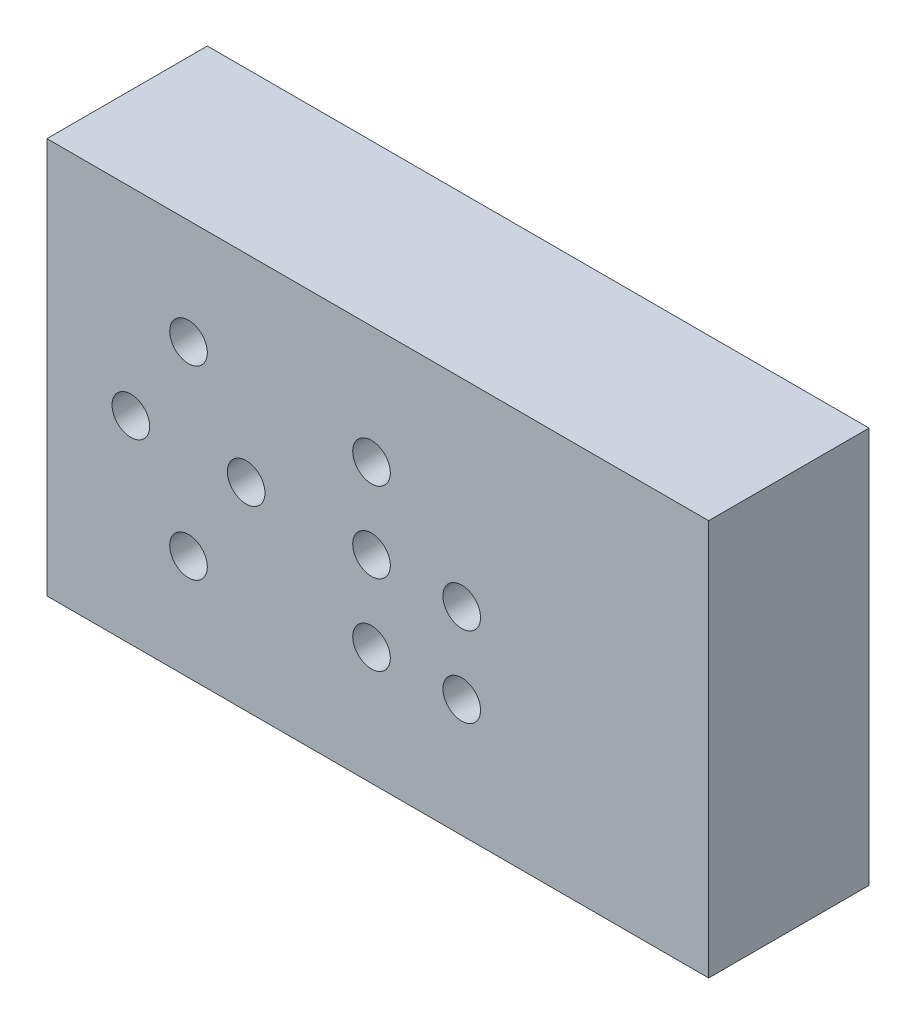
SolidWorks part; units mm, degrees
ref_plane "Front Plane" through (0, 0, 0) normal (0, 0, 1) x (1, 0, 0)
ref_plane "Top Plane" through (0, 0, 0) normal (0, 1, 0) x (1, 0, 0)
ref_plane "Right Plane" through (0, 0, 0) normal (1, 0, 0) x (0, 0, -1)
sketch "Sketch1" plane through (0, 0, 0) normal (0, 0, 1) x (1, 0, 0)
  line L10 (-73.2449, 39.5) -> (-73.2449, -39.5)
  line L14 (58.7551, 39.5) -> (58.7551, -39.5)
  line L15 (-73.2449, 39.5) -> (58.7551, 39.5)
  line L17 (58.7551, -39.5) -> (-73.2449, -39.5)
  circle A0 centre (-45, 18.5) radius 3.75
  circle A1 centre (-45, -18.5) radius 3.75
  circle A2 centre (-56.5, 0) radius 3.75
  circle A3 centre (-33.5, 0) radius 3.75
  circle A4 centre (-8.5, 0) radius 3.75
  circle A5 centre (-8.5, -16) radius 3.75
  circle A6 centre (-8.5, 16) radius 3.75
  circle A7 centre (9.5, -16) radius 3.75
  circle A8 centre (9.5, 0) radius 3.75
  point P0 (0, 0)
  point P1 (-7.2449, 39.5)
  point P2 (-7.2449, -39.5)
  dimension "D3" = 7.5
  dimension "D5" = 73.2449
  dimension "D1" = 39.5
  dimension "D2" = 79
  dimension "D4" = 132
extrude "Boss-Extrude2" add sketch "Sketch1" along normal blind 32 contours L10 L17 L14 L15
extrude "Cut-Extrude15" cut sketch "Sketch1<6>" along normal blind 42 contours A0 | A2 | A3 | A1 | A4 | A6 | A5 | A8 | A7
sketch "Sketch1<6>" plane through (0, 0, 0) normal (0, 0, 1) x (1, 0, 0) same geometry as "Sketch1"
